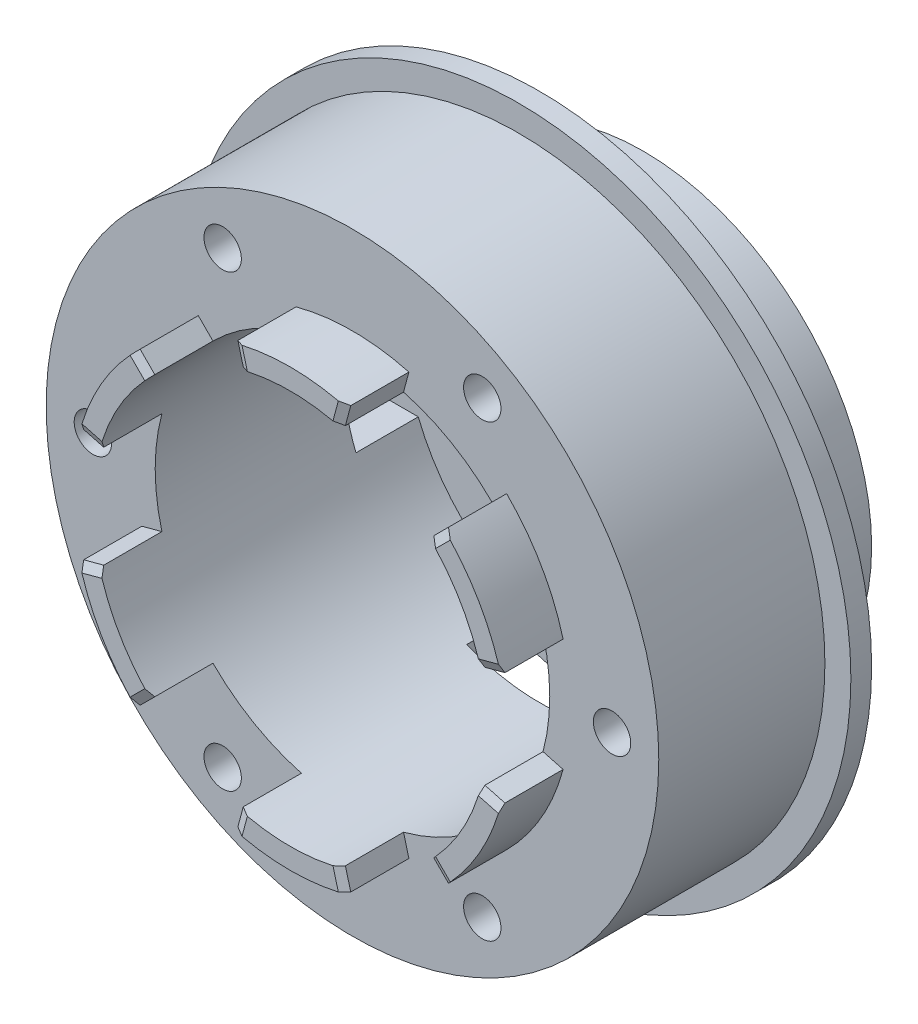
SolidWorks part; units mm, degrees
ref_plane "정면" through (0, 0, 0) normal (0, 0, 1) x (1, 0, 0)
ref_plane "윗면" through (0, 0, 0) normal (0, 1, 0) x (1, 0, 0)
ref_plane "우측면" through (0, 0, 0) normal (1, 0, 0) x (0, 0, -1)
sketch "스케치1" plane through (0, 0, 0) normal (0, 0, 1) x (1, 0, 0)
  circle A0 centre (0, 0) radius 11
  dimension "D1" = 22
extrude "보스-돌출1" add sketch "스케치1" along normal blind 2
sketch "스케치2" plane through (0, 0, 2) normal (0, 0, 1) x (1, 0, 0)
  circle A0 centre (0, 0) radius 11
  circle A1 centre (0, 0) radius 9.5
  circle A5 centre (0, 0) radius 11 construction
  dimension "D1" = 1.5
extrude "보스-돌출2" add sketch "스케치2" along normal blind 3
sketch "스케치4" plane through (0, 0, 5) normal (0, 0, 1) x (1, 0, 0)
  circle A0 centre (0, 0) radius 16
  circle A1 centre (0, 0) radius 9.5
  circle A2 centre (0, 0) radius 9.5 construction
  dimension "D1" = 32
extrude "보스-돌출3" add sketch "스케치4" along normal blind 1
sketch "스케치5" plane through (0, 0, 6) normal (0, 0, 1) x (1, 0, 0)
  circle A0 centre (0, 0) radius 9.5
  circle A1 centre (0, 0) radius 14.75
  circle A2 centre (0, 0) radius 9.5 construction
  dimension "D1" = 29.5
extrude "보스-돌출4" add sketch "스케치5" along normal blind 8
sketch "스케치6" plane through (0, 0, 14) normal (0, 0, 1) x (1, 0, 0)
  circle A0 centre (0, 0) radius 12.5 construction
  circle A6 centre (0, 0) radius 9.5 construction
  circle A8 centre (12.5, 0) radius 0.9
  circle A9 centre (6.25, -10.8253) radius 0.9
  circle A10 centre (-6.25, -10.8253) radius 0.9
  circle A11 centre (-12.5, 0) radius 0.9
  circle A12 centre (-6.25, 10.8253) radius 0.9
  circle A13 centre (6.25, 10.8253) radius 0.9
  point P6 (0, 0)
  point P19 (0, 0)
  point P20 (0, 0)
  dimension "D1" = 3
  dimension "D2" = 1.8
  dimension "D3" = 6
extrude "컷-돌출1" cut sketch "스케치6" against normal blind 8
sketch "스케치7" plane through (0, 0, 0) normal (0, 0, -1) x (-1, 0, 0)
  circle A0 centre (0, 0) radius 7 construction
  circle A5 centre (0, 0) radius 3
  circle A6 centre (-7, 0) radius 1.6
  circle A7 centre (7, 0) radius 1.6
  circle A9 centre (0, 7) radius 1.6
  circle A11 centre (0, -7) radius 1.6
  dimension "D1" = 14
  dimension "D2" = 3.2
  dimension "D4" = 6
extrude "컷-돌출2" cut sketch "스케치7" against normal through all
sketch "스케치8" plane through (0, 0, 0) normal (0, 1, 0) x (1, 0, 0)
  line L0 (11, 0) -> (-11, 0) construction
  line L1 (-3.5, -2) -> (3.5, -2)
  line L2 (-3.5, -2) -> (-3.5, -5)
  line L3 (-3.5, -5) -> (3.5, -5)
  line L4 (3.5, -2) -> (3.5, -5)
  line L5 (-3.5, -2) -> (3.5, -5) construction
  line L6 (-3.5, -5) -> (3.5, -2) construction
  line L8 (11, -5) -> (11, 0) construction
  line L9 (-11, 0) -> (-11, -5) construction
  line L10 (11, -5) -> (-11, -5) construction
  point P0 (0, -3.5)
  dimension "D1" = 2
  dimension "D3" = 7.5
  dimension "D4" = 7.5
extrude "컷-돌출3" cut sketch "스케치8" against normal through all both and the other way through all
sketch "스케치9" plane through (0, 0, 0) normal (1, 0, 0) x (0, 0, -1)
  line L0 (-5, -10.4283) -> (-5, 10.4283) construction
  line L1 (-5, -3.5) -> (-2, -3.5)
  line L2 (-5, -3.5) -> (-5, 3.5)
  line L3 (-5, 3.5) -> (-2, 3.5)
  line L4 (-2, -3.5) -> (-2, 3.5)
  line L5 (0, 11) -> (-2, 11) construction
  line L6 (-2, -11) -> (0, -11) construction
  line L7 (0, -11) -> (0, 11) construction
  dimension "D1" = 7.5
  dimension "D2" = 7.5
  dimension "D3" = 2
extrude "컷-돌출4" cut sketch "스케치9" against normal through all both and the other way through all
sketch "스케치10" plane through (0, 0, 14) normal (0, 0, 1) x (1, 0, 0)
  line L1 (2.4588, 9.1763) -> (2.7176, 10.1422)
  line L3 (6.7175, 6.7175) -> (7.4246, 7.4246)
  line L5 (9.1763, 2.4588) -> (10.1422, 2.7176)
  line L7 (9.1763, -2.4588) -> (10.1422, -2.7176)
  line L9 (6.7175, -6.7175) -> (7.4246, -7.4246)
  line L11 (2.4588, -9.1763) -> (2.7176, -10.1422)
  line L13 (-2.4588, -9.1763) -> (-2.7176, -10.1422)
  line L15 (-6.7175, -6.7175) -> (-7.4246, -7.4246)
  line L17 (-9.1763, -2.4588) -> (-10.1422, -2.7176)
  line L19 (-9.1763, 2.4588) -> (-10.1422, 2.7176)
  line L21 (-6.7175, 6.7175) -> (-7.4246, 7.4246)
  line L23 (-2.4588, 9.1763) -> (-2.7176, 10.1422)
  arc A0 (-7.4246, 7.4246) -> (-10.1422, 2.7176) centre (0, 0) ccw
  arc A1 (-9.1763, -2.4588) -> (-6.7175, -6.7175) centre (0, 0) ccw
  arc A2 (2.7176, 10.1422) -> (-2.7176, 10.1422) centre (0, 0) ccw
  arc A3 (10.1422, 2.7176) -> (7.4246, 7.4246) centre (0, 0) ccw
  arc A4 (7.4246, -7.4246) -> (10.1422, -2.7176) centre (0, 0) ccw
  arc A5 (-2.7176, -10.1422) -> (2.7176, -10.1422) centre (0, 0) ccw
  arc A6 (-10.1422, -2.7176) -> (-7.4246, -7.4246) centre (0, 0) ccw
  arc A7 (-2.4588, -9.1763) -> (2.4588, -9.1763) centre (0, 0) ccw
  arc A8 (6.7175, -6.7175) -> (9.1763, -2.4588) centre (0, 0) ccw
  arc A9 (9.1763, 2.4588) -> (6.7175, 6.7175) centre (0, 0) ccw
  arc A10 (2.4588, 9.1763) -> (-2.4588, 9.1763) centre (0, 0) ccw
  arc A11 (-6.7175, 6.7175) -> (-9.1763, 2.4588) centre (0, 0) ccw
  point P30 (0, 0)
  dimension "D1" = 1
extrude "보스-돌출5" add sketch "스케치10" along normal blind 3
chamfer "모따기1" distance 0.2 angle 64 12 edges at (-9.6593, -2.5882, 17) (-7.0711, -7.0711, 17) (-2.5882, -9.6593, 17) (2.5882, -9.6593, 17) (7.0711, -7.0711, 17) (9.6593, -2.5882, 17) (9.6593, 2.5882, 17) (7.0711, 7.0711, 17) (2.5882, 9.6593, 17) (-2.5882, 9.6593, 17) (-7.0711, 7.0711, 17) (-9.6593, 2.5882, 17) first distance on face at (-9.6593, -2.5882, 15.5) first distance on face at (-7.0711, -7.0711, 15.5) first distance on face at (-2.5882, -9.6593, 15.5) first distance on face at (2.5882, -9.6593, 15.5) first distance on face at (7.0711, -7.0711, 15.5) first distance on face at (9.6593, -2.5882, 15.5) first distance on face at (9.6593, 2.5882, 15.5) first distance on face at (7.0711, 7.0711, 15.5) first distance on face at (2.5882, 9.6593, 15.5) first distance on face at (-2.5882, 9.6593, 15.5) first distance on face at (-7.0711, 7.0711, 15.5) first distance on face at (-9.6593, 2.5882, 15.5)
